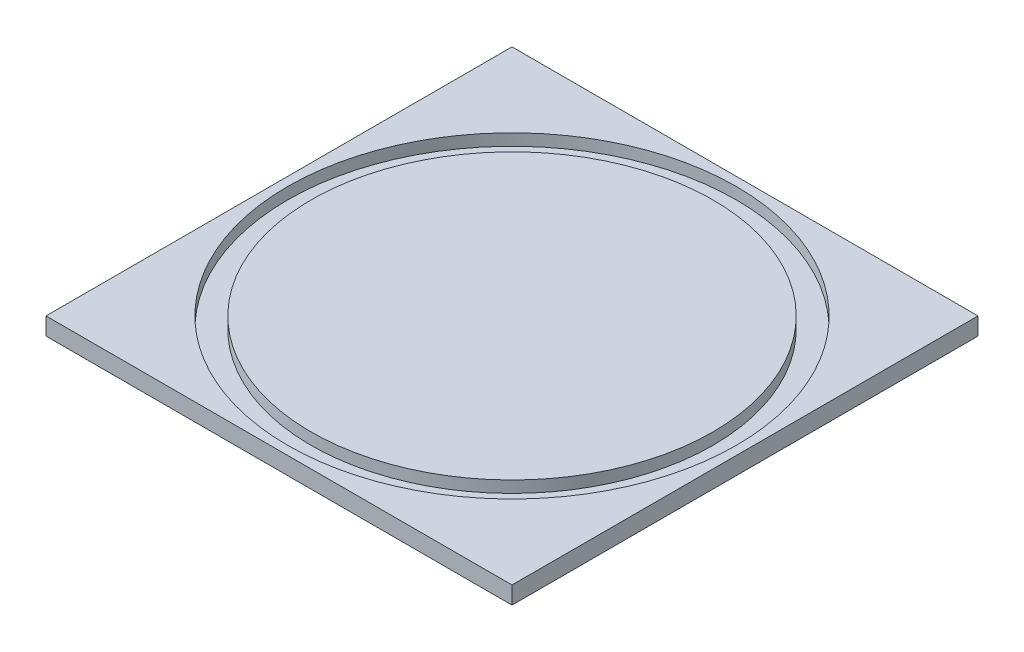
SolidWorks part; units mm, degrees
ref_plane "Front Plane" through (0, 0, 0) normal (0, 0, 1) x (1, 0, 0)
ref_plane "Top Plane" through (0, 0, 0) normal (0, 1, 0) x (1, 0, 0)
ref_plane "Right Plane" through (0, 0, 0) normal (1, 0, 0) x (0, 0, -1)
sketch "Sketch1" plane through (0, 0, 0) normal (0, 1, 0) x (1, 0, 0)
  line L0 (0, 40) -> (0, -40)
  line L1 (0, -40) -> (80, -40)
  line L2 (80, -40) -> (80, 40)
  line L3 (80, 40) -> (0, 40)
  dimension "D1" = 40
  dimension "D2" = 80
  dimension "D3" = 80
extrude "Boss-Extrude1" add sketch "Sketch1" along normal blind 3
sketch "Sketch3" plane through (0, 3, 0) normal (0, 1, 0) x (1, 0, 0)
  line L4 (80, -40) -> (80, 40) construction
  line L5 (0, -40) -> (80, -40) construction
  circle A0 centre (40, 0) radius 38.5
  dimension "D3" = 77
  dimension "D1" = 40
  dimension "D2" = 40
extrude "Cut-Extrude-Thin1" cut sketch "Sketch3" against normal blind 2 thin thin type one direction reverse wall 4
